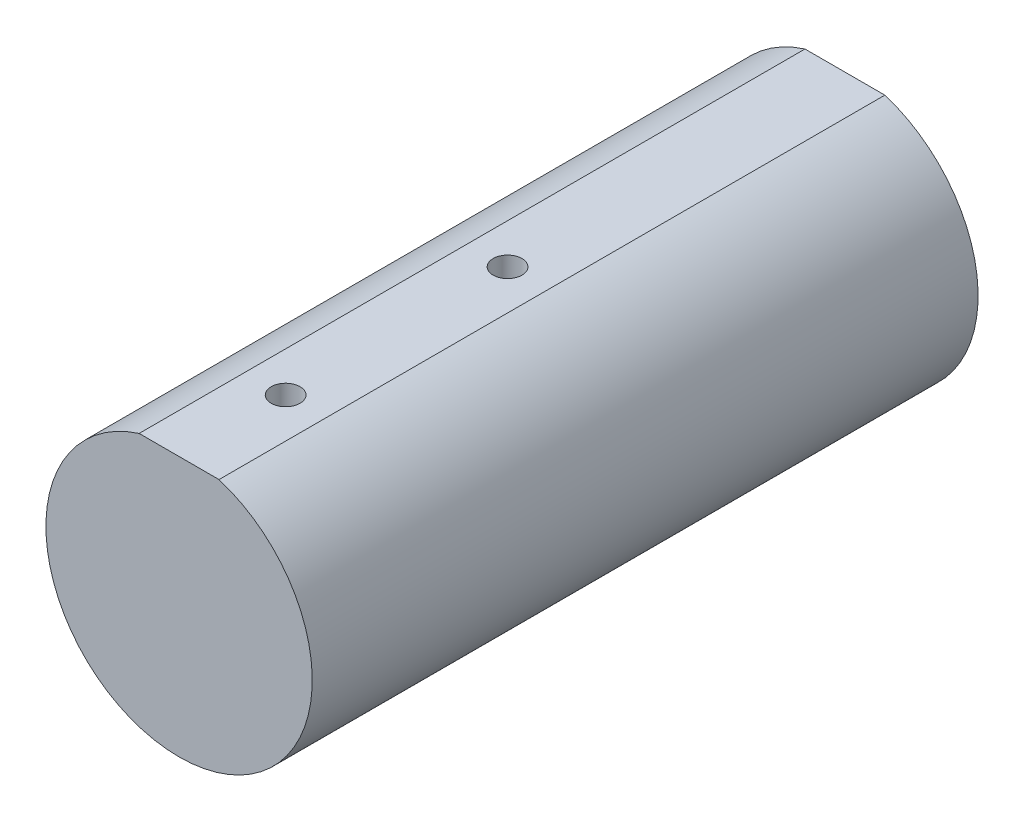
SolidWorks part; units mm, degrees
ref_plane "Front Plane" through (0, 0, 0) normal (0, 0, 1) x (1, 0, 0)
ref_plane "Top Plane" through (0, 0, 0) normal (0, 1, 0) x (1, 0, 0)
ref_plane "Right Plane" through (0, 0, 0) normal (1, 0, 0) x (0, 0, -1)
sketch "Sketch1" plane through (0, 0, 0) normal (0, 0, 1) x (1, 0, 0)
  circle A0 centre (0, 0) radius 15
  dimension "D1" = 30
extrude "Boss-Extrude1" add sketch "Sketch1" along normal mid plane 75
sketch "Sketch2" plane through (0, 0, 37.5) normal (0, 0, 1) x (1, 0, 0)
  line L0 (0, -1000) -> (0, 49000) construction
  line L1 (-4.5, 19.3091) -> (4.5, 19.3091)
  line L2 (-4.5, 19.3091) -> (-4.5, 14.3091)
  line L3 (-4.5, 14.3091) -> (4.5, 14.3091)
  line L4 (4.5, 19.3091) -> (4.5, 14.3091)
  line L5 (-4.5, 19.3091) -> (4.5, 14.3091) construction
  line L6 (-4.5, 14.3091) -> (4.5, 19.3091) construction
  circle A0 centre (0, 0) radius 15 construction
  point P0 (0, 16.8091)
  dimension "D1" = 9
  dimension "D2" = 5
extrude "Cut-Extrude1" cut sketch "Sketch2" against normal through all
sketch "Sketch3" plane through (0, 14.3091, 0) normal (0, 1, 0) x (1, 0, 0)
  line L0 (0, -1000) -> (0, 49000) construction
  line L1 (-4.5, -37.5) -> (4.5, -37.5) construction
  circle A0 centre (0, -25.5) radius 1.625
  circle A1 centre (0, -0.5) radius 1.625
  dimension "D5" = 3.25
  dimension "D6" = 3.25
  dimension "D1" = 12
  dimension "D2" = 25
extrude "Cut-Extrude2" cut sketch "Sketch3" against normal through all
sketch "Sketch4" plane through (0, 14.3091, 0) normal (0, 1, 0) x (1, 0, 0)
  circle A1 centre (0, -0.5) radius 4
  circle A2 centre (0, -25.5) radius 4
  dimension "D2" = 8
  dimension "D3" = 8
extrude "Cut-Extrude3" cut sketch "Sketch4" against normal blind 150 from offset 20 offset against normal yes
